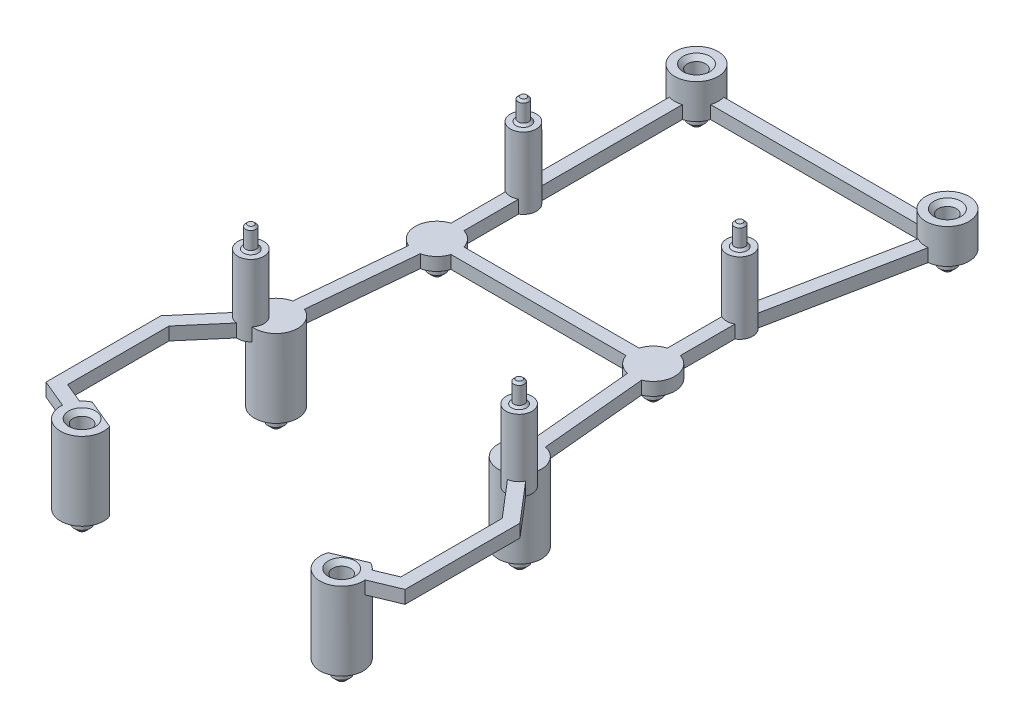
SolidWorks part; units mm, degrees
ref_plane "정면" through (0, 0, 0) normal (0, 0, 1) x (1, 0, 0)
ref_plane "윗면" through (0, 0, 0) normal (0, 1, 0) x (1, 0, 0)
ref_plane "우측면" through (0, 0, 0) normal (1, 0, 0) x (0, 0, -1)
sketch "스케치1" plane through (0, 0, 0) normal (0, 1, 0) x (1, 0, 0)
  line L0 (14.6134, 0) -> (-16.7453, 0) construction
  line L1 (0, -15.5866) -> (0, 23.5274) construction
sketch "스케치2" plane through (0, 0, 0) normal (0, 1, 0) x (1, 0, 0)
  line L1 (200014.6134, 0) -> (-200016.7453, 0) construction
  line L2 (0, -200015.5866) -> (0, 200023.5274) construction
  line L3 (0, -55) -> (0, 55) construction
  circle A0 centre (25, 35) radius 3
  circle A1 centre (31, -22) radius 3
  circle A2 centre (-31, -22) radius 3
  circle A3 centre (-25, 35) radius 3
  dimension "D3" = 6
  dimension "D6" = 6
  dimension "D1" = 22
  dimension "D2" = 31
  dimension "D4" = 35
  dimension "D5" = 25
extrude "보스-돌출1" add sketch "스케치2" along normal blind 16.5 contours A3
sketch "스케치3" plane through (0, 16.5, 0) normal (0, 1, 0) x (1, 0, 0)
  circle A2 centre (-31, -22) radius 1.2
  circle A3 centre (-31, -22) radius 1.2
  circle A5 centre (-25, 35) radius 1.2
  circle A6 centre (-25, 35) radius 1.2
  circle A8 centre (25, 35) radius 1.2
  circle A9 centre (25, 35) radius 1.2
  circle A11 centre (31, -22) radius 1.2
  circle A12 centre (31, -22) radius 1.2
  dimension "D2" = 1.8
  dimension "D1" = 1.8
  dimension "D3" = 1.8
  dimension "D4" = 1.8
extrude "보스-돌출2" add sketch "스케치3" along normal blind 5
sketch "스케치4" plane through (0, 0, 0) normal (0, -1, 0) x (1, 0, 0)
  line L0 (0, -20.4085) -> (0, 20.1177) construction
  circle A0 centre (-25, -15) radius 5
  circle A1 centre (-25, -75) radius 5 construction
  circle A2 centre (-25, -75) radius 5
  circle A3 centre (-25, -15) radius 5 construction
  circle A4 centre (25, -15) radius 5
  circle A5 centre (33, -75) radius 5 construction
  circle A6 centre (33, -75) radius 5
extrude "보스-돌출3" add sketch "스케치4" against normal blind 3 contours A0
sketch "스케치6" plane through (0, 0, 0) normal (0, 1, 0) x (1, 0, 0)
  line L0 (0, 9.9325) -> (0, -18.4072) construction
  circle A0 centre (-28.1598, -19) radius 5
  arc A1 (-28.1598, -14) -> (-28.1598, -24) centre (-28.1598, -19) ccw construction
  circle A2 centre (28.1598, -19) radius 5
extrude "보스-돌출4" add sketch "스케치6" along normal blind 3 and the other way blind 15
sketch "스케치7" plane through (0, 0, 0) normal (0, 1, 0) x (1, 0, 0)
  line L1 (32.1755, -57.4981) -> (25.274, -60.3677)
  line L2 (32.1755, -57.4981) -> (25.274, -60.3677)
  line L3 (-25.274, -60.3677) -> (-32.1755, -57.4981)
  line L4 (-25.274, -60.3677) -> (-32.1755, -57.4981)
  arc A1 (25.274, -60.3677) -> (32.1755, -57.4981) centre (30, -62) ccw
  arc A2 (25.274, -60.3677) -> (32.1755, -57.4981) centre (30, -62) ccw
  arc A3 (-32.1755, -57.4981) -> (-25.274, -60.3677) centre (-30, -62) ccw
  arc A4 (-32.1755, -57.4981) -> (-25.274, -60.3677) centre (-30, -62) ccw
  dimension "D1" = 0
  dimension "D2" = 0
extrude "보스-돌출5" add sketch "스케치7" along normal blind 3 and the other way blind 15 contours A4 L4
sketch "스케치8" plane through (0, 0, 0) normal (0, 1, 0) x (1, 0, 0)
  line L0 (-28.1598, -19) -> (-25, 15) construction
  line L1 (-25, 15) -> (-25, 35) construction
  line L3 (25, 35) -> (25, 15) construction
  line L4 (28.1598, -19) -> (25, 15) construction
  line L5 (25, 15) -> (-25, 15) construction
  line L6 (38.5, -56.8413) -> (33.8283, -58.7837)
  line L7 (34.9801, -61.5538) -> (41.5, -58.8429)
  line L8 (41.5, -58.8429) -> (41.5, -32.2881)
  line L9 (41.5, -32.2881) -> (32.4001, -21.6496)
  line L10 (30.1203, -23.5996) -> (38.5, -33.3961)
  line L11 (38.5, -33.3961) -> (38.5, -56.8413)
  line L12 (38.5, -56.8413) -> (33.8283, -58.7837)
  line L13 (34.9801, -61.5538) -> (41.5, -58.8429)
  line L14 (41.5, -58.8429) -> (41.5, -32.2881)
  line L15 (41.5, -32.2881) -> (32.4001, -21.6496)
  line L16 (30.1203, -23.5996) -> (38.5, -33.3961)
  line L17 (38.5, -33.3961) -> (38.5, -56.8413)
  line L18 (-41.5, -58.8429) -> (-34.9801, -61.5538)
  line L19 (-33.8283, -58.7837) -> (-38.5, -56.8413)
  line L20 (-38.5, -56.8413) -> (-38.5, -33.3961)
  line L21 (-38.5, -33.3961) -> (-30.1203, -23.5996)
  line L22 (-32.4001, -21.6496) -> (-41.5, -32.2881)
  line L23 (-41.5, -32.2881) -> (-41.5, -58.8429)
  line L24 (-41.5, -58.8429) -> (-34.9801, -61.5538)
  line L25 (-33.8283, -58.7837) -> (-38.5, -56.8413)
  line L26 (-38.5, -56.8413) -> (-38.5, -33.3961)
  line L27 (-38.5, -33.3961) -> (-30.1203, -23.5996)
  line L28 (-32.4001, -21.6496) -> (-41.5, -32.2881)
  line L29 (-41.5, -32.2881) -> (-41.5, -58.8429)
  line L30 (29.6534, -18.8612) -> (26.5, 15.0696)
  line L31 (-23.5, 16.5) -> (-23.5, 33.5)
  line L33 (23.5, 33.5) -> (23.5, 16.5)
  line L34 (-26.6662, -19.1388) -> (-23.6329, 13.5)
  line L35 (23.5, 16.5) -> (-23.5, 16.5)
  line L36 (26.6662, -19.1388) -> (23.6329, 13.5)
  line L37 (-26.5, 15.0696) -> (-26.5, 36.5)
  line L39 (26.5, 34.8515) -> (26.5, 15.0696)
  line L40 (-29.6534, -18.8612) -> (-26.5, 15.0696)
  line L41 (23.6329, 13.5) -> (-23.6329, 13.5)
  line L42 (29.6534, -18.8612) -> (26.6662, -19.1388)
  line L43 (-29.6534, -18.8612) -> (-26.6662, -19.1388)
  line L44 (25, 16.5) -> (-25, 16.5) construction
  line L45 (-23.5, 15) -> (-23.5, 33.5) construction
  line L46 (-26.6662, -19.1388) -> (-23.5064, 14.8612) construction
  line L47 (25, 13.5) -> (-25, 13.5) construction
  line L48 (-29.6534, -18.8612) -> (-26.4936, 15.1388) construction
  line L49 (-26.5, 15) -> (-26.5, 36.5) construction
  line L50 (29.6534, -18.8612) -> (26.4936, 15.1388) construction
  line L51 (26.5, 36.5) -> (26.5, 15) construction
  line L52 (23.5, 33.5) -> (23.5, 15) construction
  line L53 (26.6662, -19.1388) -> (23.5064, 14.8612) construction
  line L54 (23.5, 33.5) -> (23.7632, 36.4644)
  line L55 (-23.5, 33.5) -> (23.5, 33.5) construction
  line L56 (-23.5, 33.5) -> (-23.5, 33.5)
  line L57 (-25, 35) -> (25, 35) construction
  line L78 (25, 35) -> (33, 75) construction
  line L79 (33, 75) -> (-25, 75) construction
  line L80 (-25, 75) -> (-25, 35) construction
  line L81 (26.5, 34.8515) -> (34.8297, 76.5)
  line L82 (34.8297, 76.5) -> (-26.5, 76.5)
  line L83 (-26.5, 76.5) -> (-26.5, 35)
  line L84 (23.7632, 36.4644) -> (31.1703, 73.5)
  line L85 (31.1703, 73.5) -> (-23.5, 73.5)
  line L86 (-23.5, 73.5) -> (-23.5, 33.5)
  line L87 (23.5291, 35.2942) -> (31.1703, 73.5) construction
  line L88 (26.4709, 34.7058) -> (34.8297, 76.5) construction
  line L89 (-26.5, 36.5) -> (26.5, 36.5) construction
  line L90 (-23.5, 73.5) -> (-23.5, 35) construction
  circle A1 centre (25, 15) radius 5
  arc A2 (34.9801, -61.5538) -> (33.8283, -58.7837) centre (30, -62) ccw
  arc A3 (30.1203, -23.5996) -> (32.4001, -21.6496) centre (28.1598, -19) ccw
  arc A4 (34.9801, -61.5538) -> (33.8283, -58.7837) centre (30, -62) ccw
  arc A5 (30.1203, -23.5996) -> (32.4001, -21.6496) centre (28.1598, -19) ccw
  arc A6 (-33.8283, -58.7837) -> (-34.9801, -61.5538) centre (-30, -62) ccw
  arc A7 (-32.4001, -21.6496) -> (-30.1203, -23.5996) centre (-28.1598, -19) ccw
  arc A8 (-33.8283, -58.7837) -> (-34.9801, -61.5538) centre (-30, -62) ccw
  arc A9 (-32.4001, -21.6496) -> (-30.1203, -23.5996) centre (-28.1598, -19) ccw
  circle A10 centre (25, 15) radius 5 construction
  circle A11 centre (-25, 15) radius 5
  arc A12 (33.0878, -19.8457) -> (28.7347, -23.9668) centre (28.1598, -19) ccw
  arc A13 (33.0878, -19.8457) -> (28.7347, -23.9668) centre (31, -22) ccw
  arc A14 (33.0878, -19.8457) -> (28.7347, -23.9668) centre (28.1598, -19) ccw construction
  arc A15 (33.0878, -19.8457) -> (28.7347, -23.9668) centre (31, -22) ccw construction
  arc A16 (-28.7347, -23.9668) -> (-33.0878, -19.8457) centre (-31, -22) ccw
  arc A17 (-28.7347, -23.9668) -> (-33.0878, -19.8457) centre (-28.1598, -19) ccw
  arc A18 (-28.7347, -23.9668) -> (-33.0878, -19.8457) centre (-31, -22) ccw construction
  arc A19 (-28.7347, -23.9668) -> (-33.0878, -19.8457) centre (-28.1598, -19) ccw construction
  circle A20 centre (-25, 15) radius 5 construction
  circle A21 centre (-25, 35) radius 3
  arc A22 (-23.5, 37.5981) -> (-23.5, 32.4019) centre (-25, 35) ccw construction
  circle A23 centre (25, 35) radius 3
  arc A24 (23.5, 32.4019) -> (24.0387, 37.8418) centre (25, 35) ccw construction
  circle A33 centre (33, 75) radius 5
  circle A34 centre (33, 75) radius 5 construction
  circle A35 centre (-25, 75) radius 5
  circle A36 centre (-25, 75) radius 5 construction
  dimension "D1" = 0
  dimension "D2" = 0
  dimension "D3" = 0
  dimension "D4" = 0
  dimension "D5" = 0
  dimension "D6" = 0
  dimension "D7" = 0
  dimension "D8" = 0
  dimension "D9" = 1.5
  dimension "D10" = 1.5
  dimension "D11" = 0
  dimension "D12" = 0
  dimension "D13" = 1.5
  dimension "D14" = 1.5
extrude "보스-돌출6" add sketch "스케치8" along normal blind 3
sketch "스케치9" plane through (0, -15, 0) normal (0, -1, 0) x (1, 0, 0)
  line L0 (0, -8.6201) -> (0, 27.4221) construction
  circle A1 centre (28.1598, 19) radius 1.9
  circle A4 centre (30, 62) radius 1.9
  circle A6 centre (28.1598, 19) radius 5 construction
  arc A7 (32.1755, 57.4981) -> (25.274, 60.3677) centre (30, 62) ccw construction
  circle A8 centre (-28.1598, 19) radius 1.9
  circle A9 centre (-30, 62) radius 1.9
  dimension "D1" = 3.8
  dimension "D2" = 3.8
extrude "보스-돌출7" add sketch "스케치9" along normal blind 4
sketch "스케치10" plane through (0, 0, 0) normal (0, -1, 0) x (1, 0, 0)
  line L0 (0, -6.3268) -> (0, -49.6377) construction
  circle A0 centre (25, -15) radius 1.9
  circle A1 centre (33, -75) radius 1.9
  circle A2 centre (-25, -75) radius 1.9
  arc A3 (26.5, -19.7697) -> (26.9349, -10.3896) centre (25, -15) ccw construction
  arc A4 (-26.5, -70.2303) -> (-20.2303, -76.5) centre (-25, -75) ccw construction
  arc A5 (28.2303, -76.5) -> (33.5355, -70.0288) centre (33, -75) ccw construction
  circle A6 centre (-25, -15) radius 1.9
  dimension "D1" = 3.8
  dimension "D2" = 3.8
  dimension "D3" = 3.8
extrude "보스-돌출8" add sketch "스케치10" along normal blind 4
chamfer "모따기1" distance 1 angle 45 8 edges at (-30, -19, 63.9) (30, -19, 60.1) (28.1598, -19, 17.1) (-28.1598, -19, 20.9) (-25, -4, -13.1) (25, -4, -16.9) (-25, -4, -76.9) (33, -4, -76.9)
sketch "스케치11" plane through (0, 3, 0) normal (0, 1, 0) x (1, 0, 0)
  circle A0 centre (33, 75) radius 5
  circle A1 centre (-25, 75) radius 5
  arc A2 (-20.2303, 76.5) -> (-26.5, 70.2303) centre (-25, 75) ccw construction
  arc A3 (33.5355, 70.0288) -> (28.2303, 76.5) centre (33, 75) ccw construction
extrude "보스-돌출9" add sketch "스케치11" along normal blind 5
sketch "스케치12" plane through (0, 3, 0) normal (0, 1, 0) x (1, 0, 0)
  line L0 (0, -6.3084) -> (0, 24.3722) construction
  circle A1 centre (30, -62) radius 2.1
  arc A2 (25.274, -60.3677) -> (34.9801, -61.5538) centre (30, -62) ccw construction
  circle A3 centre (-30, -62) radius 2.1
  dimension "D1" = 4.2
extrude "컷-돌출1" cut sketch "스케치12" against normal blind 5
sketch "스케치13" plane through (0, 8, 0) normal (0, 1, 0) x (1, 0, 0)
  circle A2 centre (33, 75) radius 2.1
  circle A3 centre (33, 75) radius 2.1
  circle A5 centre (-25, 75) radius 2.1
  circle A6 centre (-25, 75) radius 2.1
  dimension "D1" = 2.9
  dimension "D2" = 2.9
extrude "컷-돌출2" cut sketch "스케치13" against normal blind 4
chamfer "모따기2" distance 1 angle 45 4 edges at (33, 8, -72.9) (-25, 8, -72.9) (-30, 3, 59.9) (30, 3, 64.1)
chamfer "모따기3" distance 0.5 angle 45 8 edges at (31, 21.5, 23.2) (25, 21.5, -33.8) (-25, 21.5, -33.8) (-31, 21.5, 23.2) (25, 16.5, -33.8) (-25, 16.5, -33.8) (-31, 16.5, 23.2) (31, 16.5, 23.2)
